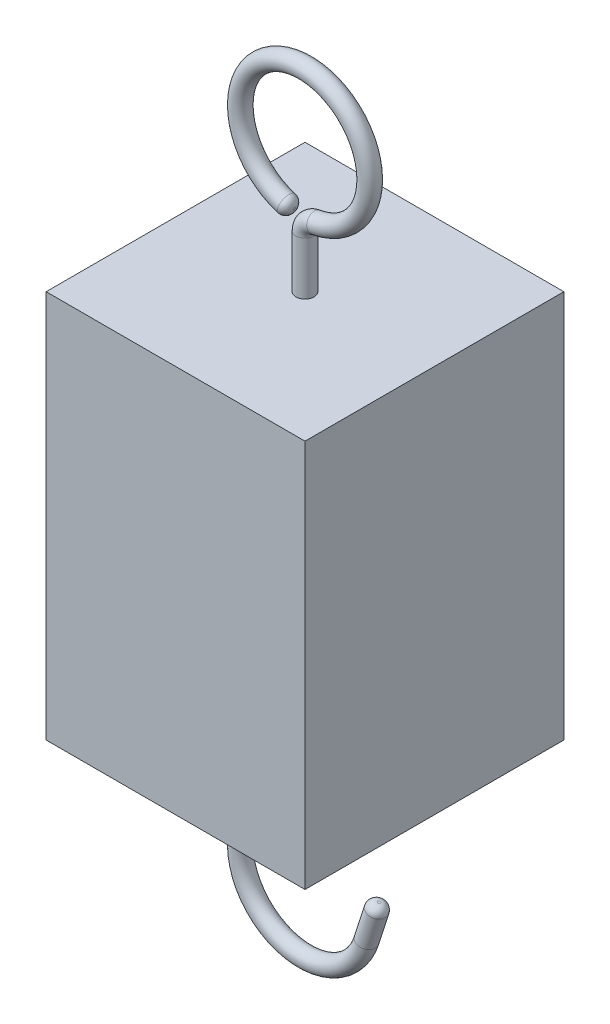
SolidWorks part; units mm, degrees
ref_plane "Front Plane" through (0, 0, 0) normal (0, 0, 1) x (1, 0, 0)
ref_plane "Top Plane" through (0, 0, 0) normal (0, 1, 0) x (1, 0, 0)
ref_plane "Right Plane" through (0, 0, 0) normal (1, 0, 0) x (0, 0, -1)
sketch "Sketch2" plane through (0, 0, 0) normal (0, 1, 0) x (1, 0, 0)
  line L1 (-50, 50) -> (50, 50)
  line L2 (-50, 50) -> (-50, -50)
  line L3 (-50, -50) -> (50, -50)
  line L4 (50, 50) -> (50, -50)
  line L5 (-50, 50) -> (50, -50) construction
  line L6 (-50, -50) -> (50, 50) construction
  point P0 (0, 0)
  dimension "D1" = 100
extrude "Boss-Extrude1" add sketch "Sketch2" along normal mid plane 150
sketch "Sketch3" plane through (0, 0, 0) normal (0, 0, 1) x (1, 0, 0)
  line L0 (0, 75) -> (0, 95.3582)
  line L1 (-50, 75) -> (50, 75) construction
  line L2 (50, 150) -> (-50, 150) construction
  arc A0 (0, 95.3582) -> (-4.217, 100.3582) centre (-5.0727, 95.3582) ccw
  arc A1 (-4.217, 100.3582) -> (4.217, 100.3582) centre (0, 125) cw
  arc A2 (0, 95.3582) -> (4.217, 100.3582) centre (5.0727, 95.3582) cw
  point P9 (0, 0)
  point P11 (0, 105.1528)
  point P12 (11.6747, 195)
  point P15 (0, 150)
  dimension "D1" = 30.0727
  dimension "D3" = 25
  dimension "D2" = 5
  dimension "D4" = 75
  dimension "D5" = 100
sweep "Sweep2" add path "Sketch3" circular profile diameter 7 parameters "D3"=7
fillet "Fillet1" radius 3 1 edges at (-3.6266, 103.8081, 0)
sketch "Sketch29" plane through (0, 0, 0) normal (0, 0, 1) x (1, 0, 0)
  line L0 (0, -75) -> (0, -82.0839)
  line L1 (-50, -75) -> (50, -75) construction
  line L2 (23.8153, -130) -> (28.6052, -115)
  arc A0 (0, -82.0839) -> (-11.1111, -100) centre (-20, -82.0839) cw
  arc A1 (-11.1111, -100) -> (23.8153, -130) centre (0, -122.3952) ccw
  point P9 (-3.3414, -124.3979)
  point P10 (-15.2641, -99.8073)
  point P12 (5.9165, -117.2099)
  point P13 (14.2942, -106.5138)
  point P14 (-11.6351, -99.0298)
  point P15 (0, 0)
  point P16 (29.9254, -107.0874)
  dimension "D1" = 20
  dimension "D2" = 25
  dimension "D3" = 25
  dimension "D4" = 15
  dimension "D5" = 55
sweep "Sweep3" add path "Sketch29" circular profile diameter 7 parameters "D3"=7
fillet "Fillet2" radius 3 1 edges at (31.9393, -116.0647, 0)
